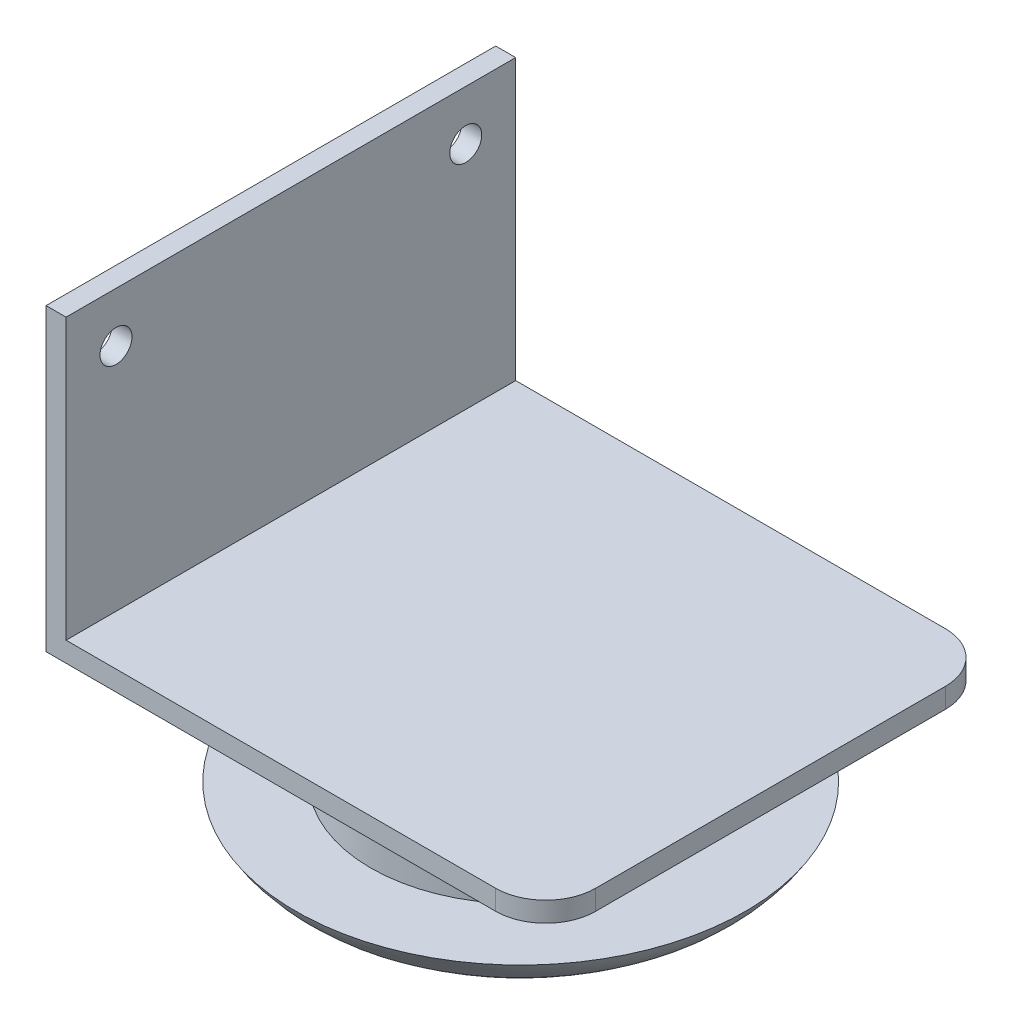
SolidWorks part; units mm, degrees
ref_plane "正面" through (0, 0, 0) normal (0, 0, 1) x (1, 0, 0)
ref_plane "平面" through (0, 0, 0) normal (0, 1, 0) x (1, 0, 0)
ref_plane "右側面" through (0, 0, 0) normal (1, 0, 0) x (0, 0, -1)
sketch "ｽｹｯﾁ1" plane through (0, 0, 0) normal (0, 0, 1) x (1, 0, 0)
  line L0 (0, 30) -> (0, 0)
  line L1 (0, 0) -> (50, 0)
  line L2 (2, 30) -> (2, 2)
  line L3 (2, 2) -> (50, 2)
  line L4 (0, 30) -> (2, 30)
  line L5 (50, 2) -> (50, 0)
  dimension "D1" = 30
  dimension "D2" = 50
  dimension "D3" = 2
extrude "ﾎﾞｽ - 押し出し1" add sketch "ｽｹｯﾁ1" along normal blind 45
sketch "ｽｹｯﾁ2" plane through (0, 0, 0) normal (-1, 0, 0) x (0, 0, 1)
  line L0 (45, 30) -> (45, 0) construction
  line L1 (45, 30) -> (0, 30) construction
  circle A0 centre (40, 25) radius 1.6
  circle A1 centre (5, 25) radius 1.6
  dimension "D1" = 35
  dimension "D3" = 3.2
  dimension "D4" = 3.2
  dimension "D5" = 5
  dimension "D6" = 5
  dimension "D2" = 5
extrude "ｶｯﾄ - 押し出し1" cut sketch "ｽｹｯﾁ2" against normal blind 35
sketch "ｽｹｯﾁ3" plane through (0, 0, 0) normal (0, -1, 0) x (1, 0, 0)
  line L0 (50, 45) -> (50, 0) construction
  line L1 (0, 45) -> (50, 45) construction
  circle A0 centre (25, 22.5) radius 15
  dimension "D1" = 30
  dimension "D2" = 25
  dimension "D3" = 22.5
fillet "ﾌｨﾚｯﾄ1" radius 5 2 edges at (50, 1, 0) (50, 1, 45)
extrude "ﾎﾞｽ - 押し出し2" add sketch "ｽｹｯﾁ3" along normal blind 10
sketch "ｽｹｯﾁ7" plane through (0, -10, 0) normal (0, -1, 0) x (-1, 0, 0)
  circle A0 centre (-25, -22.5) radius 22.5
  dimension "D1" = 45
extrude "ﾎﾞｽ - 押し出し3" add sketch "ｽｹｯﾁ7" along normal blind 5
fillet "ﾌｨﾚｯﾄ2" radius 10 1 edges at (25, -15, 0)
